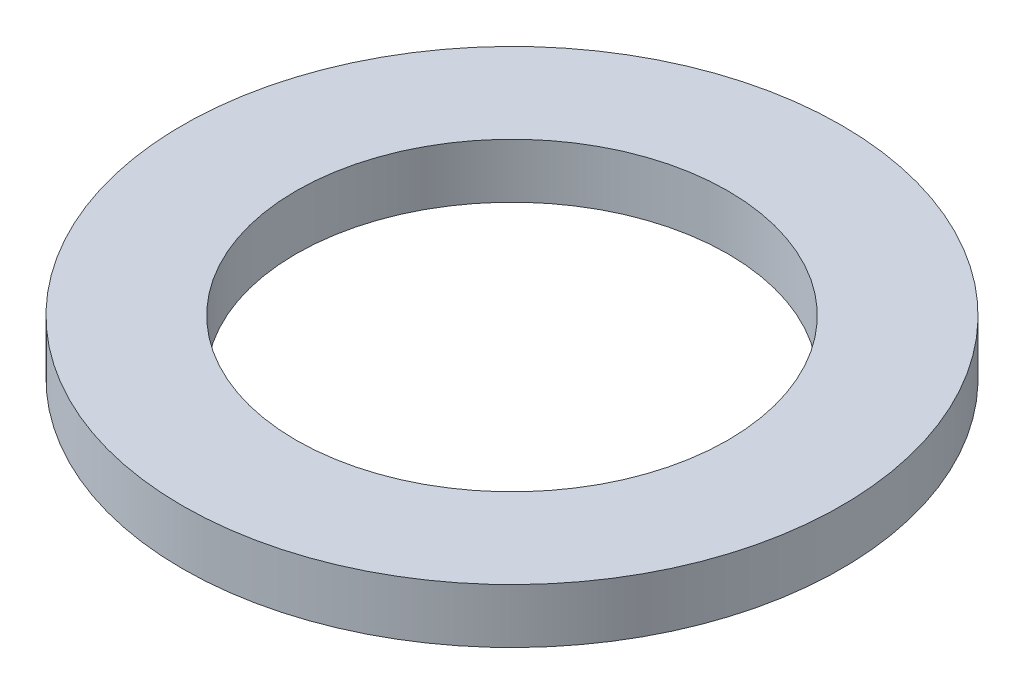
SolidWorks part; units mm, degrees
ref_plane "Front Plane" through (0, 0, 0) normal (0, 0, 1) x (1, 0, 0)
ref_plane "Top Plane" through (0, 0, 0) normal (0, 1, 0) x (1, 0, 0)
ref_plane "Right Plane" through (0, 0, 0) normal (1, 0, 0) x (0, 0, -1)
sketch "Sketch1" plane through (0, 0, 0) normal (0, 1, 0) x (1, 0, 0)
  circle A0 centre (0, 0) radius 72.5
  dimension "FLANGE_OD" = 145
extrude "Boss-Extrude1" add sketch "Sketch1" along normal blind 12
sketch "Sketch2" plane through (0, 0, 0) normal (0, 1, 0) x (1, 0, 0)
  circle A0 centre (0, 0) radius 47.5
  dimension "BORE_D" = 95
extrude "Cut-Extrude1" cut sketch "Sketch2" along normal through all
sketch "Sketch3" plane through (0, 12, 0) normal (0, 1, 0) x (1, 0, 0)
  circle A0 centre (0, 0) radius 27.9701 construction
  circle A1 centre (-27.9701, 0) radius 3.1918
  dimension "BOLT_D" = 6.3835
  dimension "BOLT_PCD" = 55.9403
extrude "Cut-Extrude2" cut sketch "Sketch3" against normal blind 9.917 rebuild error yes
pattern_circular "CirPattern1" count 6 over 360 rebuild error yes
